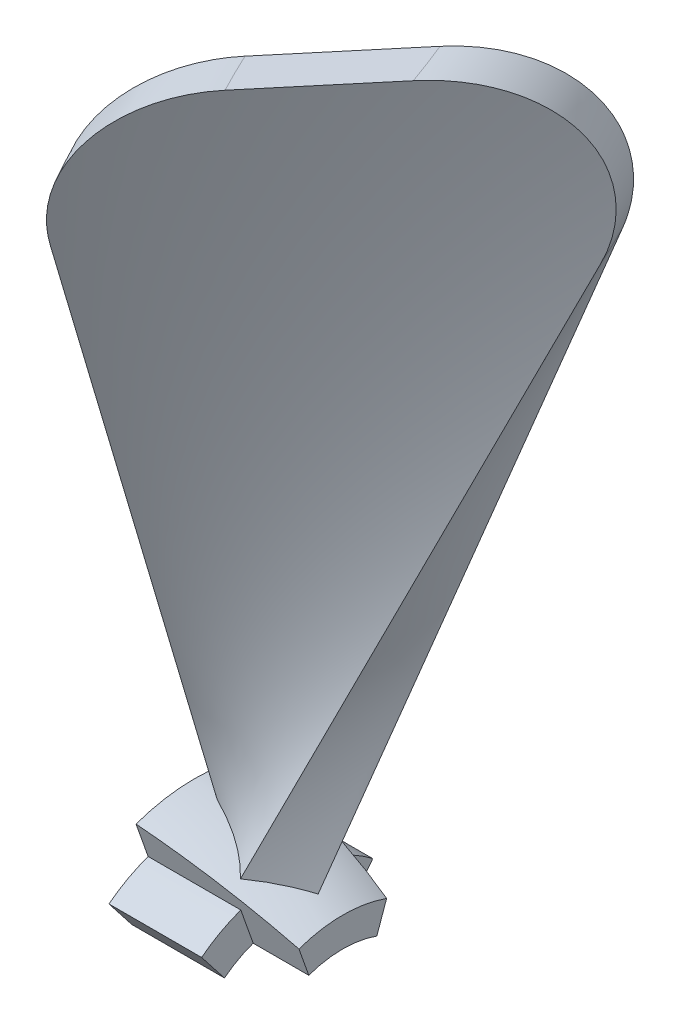
SolidWorks part; units mm, degrees
ref_plane "Спереди" through (0, 0, 0) normal (0, 0, 1) x (1, 0, 0)
ref_plane "Сверху" through (0, 0, 0) normal (0, 1, 0) x (1, 0, 0)
ref_plane "Справа" through (0, 0, 0) normal (1, 0, 0) x (0, 0, -1)
sketch "Эскиз2" plane through (0, 0, 0) normal (0, 0, 1) x (1, 0, 0)
  line L1 (1, 0) -> (28.5, 0)
  line L2 (-1000, 0) -> (49000, 0) construction
  line L3 (28.5, 0) -> (52.3107, 0)
  line L4 (1, 0) -> (1, 28.365)
  spline S0 degree 3 poles (1, 28.365) (21.4302, 25.4927) (38.5338, 16.0377) (52.3107, 0) knots 0.016012 0.016012 0.016012 0.016012 1 1 1 1
revolve "Повернуть1" add sketch "Эскиз2" angle 360 about L2
sketch "Эскиз3" plane through (0, 0, 0) normal (0, 1, 0) x (1, 0, 0)
  line L0 (-1000, 0) -> (49000, 0) construction
  line L1 (16.1294, 0.1091) -> (-47734.5616, -14827.9559) construction
  line L3 (-5.6255, -4.5523) -> (-47756.3165, -14832.6173) construction
  line L4 (14.9853, 1.848) -> (15.5785, -0.062)
  line L5 (15.5785, -0.062) -> (16.9582, 0.3664)
  line L6 (16.9582, 0.3664) -> (16.3651, 2.2764)
  line L7 (16.3651, 2.2764) -> (14.9853, 1.848)
ref_plane "Плоскость4" through (0, 0, 0) normal (0, -1, 0) x (-1, 0, 0)
ref_plane "Плоскость5" through (0, 140, 0) normal (0, -1, 0) x (-1, 0, 0)
sketch "Эскиз5" plane through (0, 140, 0) normal (0, 1, 0) x (1, 0, 0)
  line L0 (-134.8999, -185.4311) -> (-32274.2804, -38487.6532) construction
  line L1 (-134.5098, -195.1229) -> (-32273.8903, -38497.345) construction
  line L2 (-2.5137, -27.6594) -> (2.4875, -31.8558)
  line L3 (2.4875, -31.8558) -> (54.9167, 30.6269)
  line L4 (54.9167, 30.6269) -> (49.9155, 34.8233)
  line L5 (49.9155, 34.8233) -> (-2.5137, -27.6594)
ref_plane "Плоскость6" through (0, 10, 0) normal (0, -1, 0) x (-1, 0, 0)
ref_plane "Плоскость7" through (0, 20, 0) normal (0, -1, 0) x (-1, 0, 0)
sketch "Эскиз6" plane through (0, 20, 0) normal (0, -1, 0) x (-1, 0, 0)
  line L0 (-1030.8842, 1.4985) -> (48969.1158, 1.4985) construction
  line L1 (-18.9804, -3.0446) -> (-38321.2026, 32136.3359) construction
  line L2 (-27.9607, 20.7259) -> (-38330.1828, 32160.1063) construction
  line L3 (-12.9213, 8.1064) -> (-20.9156, -1.4208)
  line L4 (-20.9156, -1.4208) -> (-13.2926, -7.8172)
  line L5 (-13.2926, -7.8172) -> (-5.2984, 1.71)
  line L6 (-5.2984, 1.71) -> (-12.9213, 8.1064)
loft "По сечениям6" add profiles "Эскиз5", "Эскиз6" connector at (54.9167, 140, -30.6269) connector at (13.2926, 20, 7.8172)
fillet "Скругление3" radius 20 2 edges
sketch "Эскиз7" plane through (0, 0, 0) normal (-1, 0, 0) x (0, 0, 1)
  circle A0 centre (0, 0) radius 12.6
extrude "Вырез-Вытянуть1" cut sketch "Эскиз7" against normal blind 10
sketch "Эскиз8" plane through (0, 0, 0) normal (-1, 0, 0) x (0, 0, 1)
  circle A0 centre (0, 0) radius 16.5
extrude "Вырез-Вытянуть2" cut sketch "Эскиз8" against normal blind 2
sketch "Эскиз9" plane through (0, 0, 0) normal (-1, 0, 0) x (0, 0, 1)
  line L0 (0, 0) -> (-826.3977, 49931.3531) construction
  line L1 (-10.8982, 140) -> (6.264, 140) construction
  line L6 (-10.6565, 30.0932) -> (-5.5078, 15.5536)
  line L7 (5.5078, 15.5536) -> (10.6565, 30.0932)
  line L8 (0, 0) -> (-16690.343, 47132.0746) construction
  line L9 (0, 0) -> (16690.343, 47132.0746) construction
  circle A0 centre (0, 0) radius 16.5 construction
  arc A4 (-5.5078, 15.5536) -> (5.5078, 15.5536) centre (0, 0) cw
  circle A5 centre (0, 0) radius 31.9243 construction
  arc A6 (-10.6565, 30.0932) -> (10.6565, 30.0932) centre (0, 0) ccw
  point P5 (-2.3171, 140)
extrude "Вырез-Вытянуть3" cut sketch "Эскиз9" against normal blind 25
sketch "Эскиз10" plane through (25, 0, 0) normal (-1, 0, 0) x (0, 0, 1)
  circle A0 centre (0, 0) radius 21.2536
extrude "Вырез-Вытянуть4" cut sketch "Эскиз10" against normal blind 40
sketch "Эскиз11" plane through (1, 0, 0) normal (-1, 0, 0) x (0, 0, 1)
  line L0 (0, 0) -> (-16685.5161, 47118.4438) construction
  line L1 (0, 0) -> (16263.5547, 47281.0405) construction
  line L3 (0, 0) -> (-35355.3391, 35355.3391) construction
  line L4 (0, 0) -> (-30783.0738, 39400.5377) construction
  line L5 (0, 0) -> (30783.0738, 39400.5377) construction
  line L6 (-10.1584, 13.0022) -> (-13.8524, 17.7302)
  line L7 (10.1584, 13.0022) -> (13.8524, 17.7302)
  circle A0 centre (0, 0) radius 16.5 construction
  circle A1 centre (0, 0) radius 22.5 construction
  arc A2 (-13.8524, 17.7302) -> (13.8524, 17.7302) centre (0, 0) cw
  arc A3 (10.1584, 13.0022) -> (-10.1584, 13.0022) centre (0, 0) ccw
extrude "Бобышка-Вытянуть1" add sketch "Эскиз11" against normal blind 15
